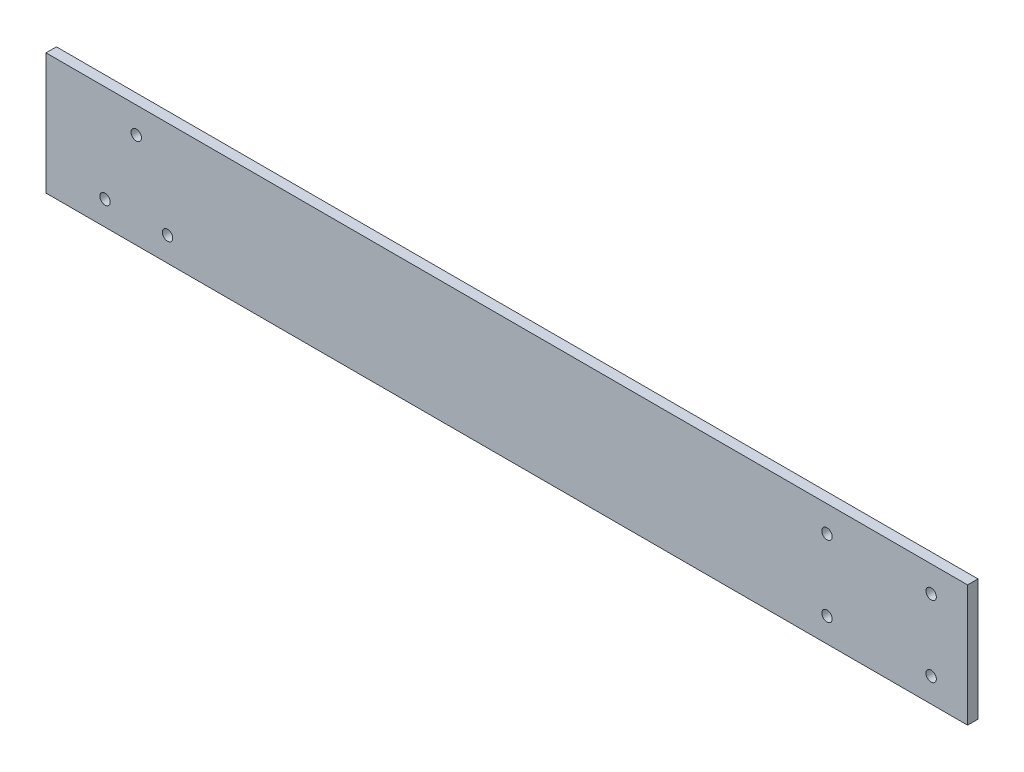
SolidWorks part; units mm, degrees
material "MDF"
ref_plane "Alzado" through (0, 0, 0) normal (0, 0, 1) x (1, 0, 0)
ref_plane "Planta" through (0, 0, 0) normal (0, 1, 0) x (1, 0, 0)
ref_plane "Vista lateral" through (0, 0, 0) normal (1, 0, 0) x (0, 0, -1)
sketch "Croquis1" plane through (0, 0, 0) normal (0, 0, 1) x (1, 0, 0)
  line L1 (-132.75, 17.5) -> (132.75, 17.5)
  line L2 (-132.75, 17.5) -> (-132.75, -17.5)
  line L3 (-132.75, -17.5) -> (132.75, -17.5)
  line L4 (132.75, 17.5) -> (132.75, -17.5)
  line L5 (-132.75, 17.5) -> (132.75, -17.5) construction
  line L6 (-132.75, -17.5) -> (132.75, 17.5) construction
  circle A1 centre (-115.75, -10.5) radius 1.5
  circle A2 centre (-97.75, -10.5) radius 1.5
  circle A3 centre (-106.75, 10) radius 1.5
  circle A4 centre (122.25, 10) radius 1.5
  circle A5 centre (92.25, 10) radius 1.5
  circle A6 centre (92.25, -10.5) radius 1.5
  circle A7 centre (122.25, -10.5) radius 1.5
  point P0 (0, 0)
  dimension "D3" = 3
  dimension "D1" = 35
  dimension "D2" = 265.5
  dimension "D4" = 27.5
  dimension "D5" = 26
  dimension "D6" = 7
  dimension "D7" = 17
  dimension "D8" = 18
  dimension "D9" = 10.5
  dimension "D10" = 27.5
  dimension "D13" = 30
  dimension "D14" = 7
  dimension "D11" = 2
  dimension "D12" = 2
extrude "Saliente-Extruir1" add sketch "Croquis1" along normal blind 3
